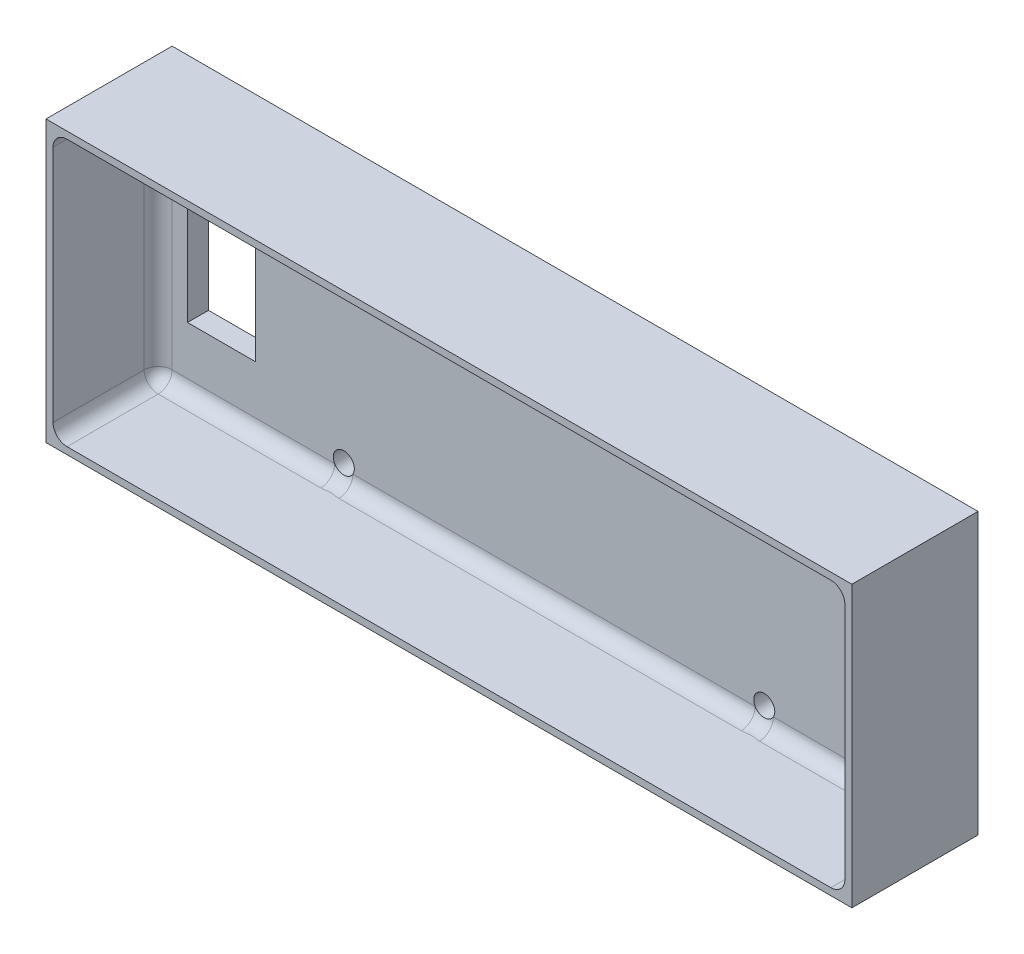
SolidWorks part; units mm, degrees
ref_plane "Front Plane" through (0, 0, 0) normal (0, 0, 1) x (1, 0, 0)
ref_plane "Top Plane" through (0, 0, 0) normal (0, 1, 0) x (1, 0, 0)
ref_plane "Right Plane" through (0, 0, 0) normal (1, 0, 0) x (0, 0, -1)
sketch "Sketch1" plane through (0, 0, 0) normal (0, 0, 1) x (1, 0, 0)
  line L1 (-57.5, 20) -> (57.5, 20)
  line L2 (-57.5, 20) -> (-57.5, -20)
  line L3 (-57.5, -20) -> (57.5, -20)
  line L4 (57.5, 20) -> (57.5, -20)
  line L5 (-57.5, 20) -> (57.5, -20) construction
  line L6 (-57.5, -20) -> (57.5, 20) construction
  circle A0 centre (-30, 16.25) radius 1.5
  circle A1 centre (30, 16.25) radius 1.5
  circle A2 centre (-30, -16.25) radius 1.5
  circle A3 centre (30, -16.25) radius 1.5
  point P0 (0, 0)
extrude "Boss-Extrude5" add sketch "Sketch1" along normal blind 3
sketch "Sketch4" plane through (0, 0, 3) normal (0, 0, 1) x (1, 0, 0)
  line L1 (-57.5, 20) -> (57.5, 20)
  line L2 (-57.5, 20) -> (-57.5, -20)
  line L3 (-57.5, -20) -> (57.5, -20)
  line L4 (57.5, 20) -> (57.5, -20)
  line L5 (-57.5, 20) -> (57.5, -20) construction
  line L6 (-57.5, -20) -> (57.5, 20) construction
  line L7 (-56.5, 19) -> (56.5, 19)
  line L8 (-56.5, 19) -> (-56.5, -19)
  line L9 (-56.5, -19) -> (56.5, -19)
  line L10 (56.5, 19) -> (56.5, -19)
  line L11 (-56.5, 19) -> (56.5, -19) construction
  line L12 (-56.5, -19) -> (56.5, 19) construction
  point P0 (0, 0)
  point P7 (0, 0)
extrude "Boss-Extrude6" add sketch "Sketch4" along normal blind 15
fillet "Fillet1" radius 2 8 edges at (56.5, -19, 10.5) (56.5, 0, 3) (0, -19, 3) (0, 19, 3) (-56.5, 0, 3) (-56.5, -19, 10.5) (-56.5, 19, 10.5) (56.5, 19, 10.5)
sketch "Sketch5" plane through (0, 0, 3) normal (0, 0, 1) x (1, 0, 0)
  line L1 (-52.3084, 10.0567) -> (-42.5765, 10.0567)
  line L2 (-52.3084, 10.0567) -> (-52.3084, -10.0567)
  line L3 (-52.3084, -10.0567) -> (-42.5765, -10.0567)
  line L4 (-42.5765, 10.0567) -> (-42.5765, -10.0567)
  line L5 (-52.3084, 10.0567) -> (-42.5765, -10.0567) construction
  line L6 (-52.3084, -10.0567) -> (-42.5765, 10.0567) construction
  point P0 (-47.4424, 0)
extrude "Cut-Extrude1" cut sketch "Sketch5" against normal blind 3
